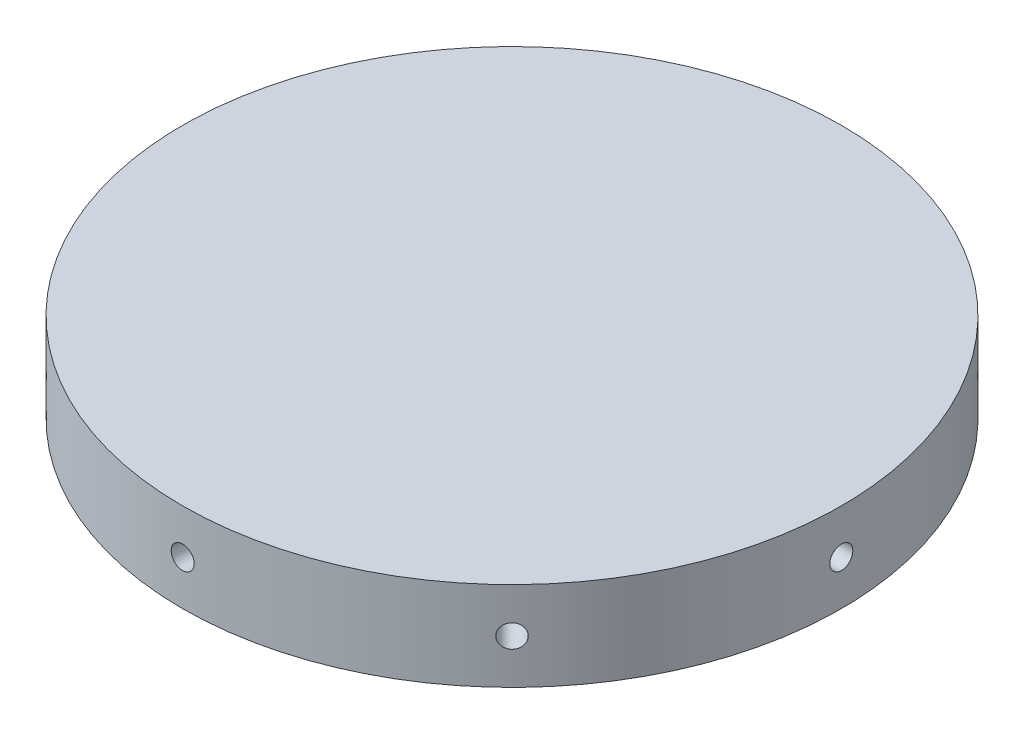
SolidWorks part; units mm, degrees
material "6061 Alloy"
ref_plane "Front Plane" through (0, 0, 0) normal (0, 0, 1) x (1, 0, 0)
ref_plane "Top Plane" through (0, 0, 0) normal (0, 1, 0) x (1, 0, 0)
ref_plane "Right Plane" through (0, 0, 0) normal (1, 0, 0) x (0, 0, -1)
sketch "Sketch1" plane through (0, 0, 0) normal (0, 1, 0) x (1, 0, 0)
  circle A0 centre (0, 0) radius 46.99
  dimension "D1" = 93.98
extrude "Bulkhead Extrusion" add sketch "Sketch1" along normal blind 12.7
ref_plane "Plane1" through (0, 0, 46.99) normal (0, 0, 1) x (1, 0, 0)
sketch "Sketch2" plane through (0, 0, 46.99) normal (0, 0, 1) x (1, 0, 0)
  line L0 (0, 12.7) -> (0, 0) construction
  line L1 (46.99, 12.7) -> (-46.99, 12.7) construction
  circle A0 centre (0, 6.35) radius 1.6383
  dimension "D1" = 3.2766
extrude "Screw Hole" cut sketch "Sketch2" against normal blind 12.7
pattern_circular "CirPattern1" count 8 over 360 about axis through (0, 12.7, 0) along (0, -1, 0) of "Screw Hole" reverse direction yes
